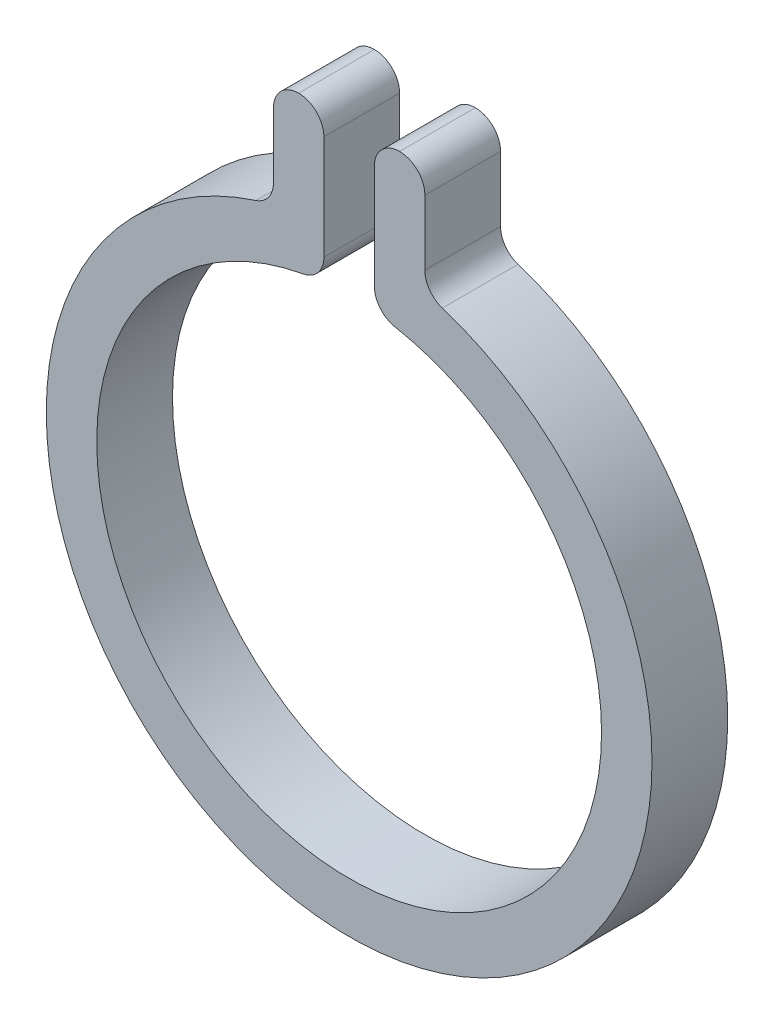
SolidWorks part; units mm, degrees
ref_plane "Front Plane" through (0, 0, 0) normal (0, 0, 1) x (1, 0, 0)
ref_plane "Top Plane" through (0, 0, 0) normal (0, 1, 0) x (1, 0, 0)
ref_plane "Right Plane" through (0, 0, 0) normal (1, 0, 0) x (0, 0, -1)
sketch "Sketch1" plane through (0, 0, 0) normal (0, 0, 1) x (1, 0, 0)
  line L0 (2, 31.8919) -> (6, 31.8919)
  line L4 (2, 19.8997) -> (2, 31.8919)
  line L8 (-6, 23.2379) -> (-6, 31.8919)
  line L9 (-6, 31.8919) -> (-2, 31.8919)
  line L10 (6, 23.2379) -> (6, 31.8919)
  line L12 (-2, 23.964) -> (-1.977, 23.9184) construction
  line L15 (1.977, 23.9184) -> (2, 23.964) construction
  line L16 (-2, 19.8997) -> (-2, 31.8919)
  arc A0 (-2, 19.8997) -> (2, 19.8997) centre (0, 0) ccw
  arc A1 (-1.977, 23.9184) -> (-2, 23.9165) centre (0, 0) ccw
  arc A2 (2, 23.9165) -> (1.977, 23.9184) centre (0, 0) ccw
  arc A3 (-6, 23.2379) -> (6, 23.2379) centre (0, 0) ccw
  point P3 (0, 20)
  point P9 (0, 20)
  dimension "D1" = 40
  dimension "D4" = 48
  dimension "D3" = 12
extrude "Boss-Extrude1" add sketch "Sketch1" along normal blind 6 contours L8 A3 L10 L0 L4 A0 L16 L9 region at (4, 31.1551, 0)
fillet "Fillet1" radius 2 8 edges at (-2, 19.8997, 3) (2, 19.8997, 3) (6, 23.2379, 3) (-6, 23.2379, 3) (6, 31.8919, 3) (2, 31.8919, 3) (-2, 31.8919, 3) (-6, 31.8919, 3)
